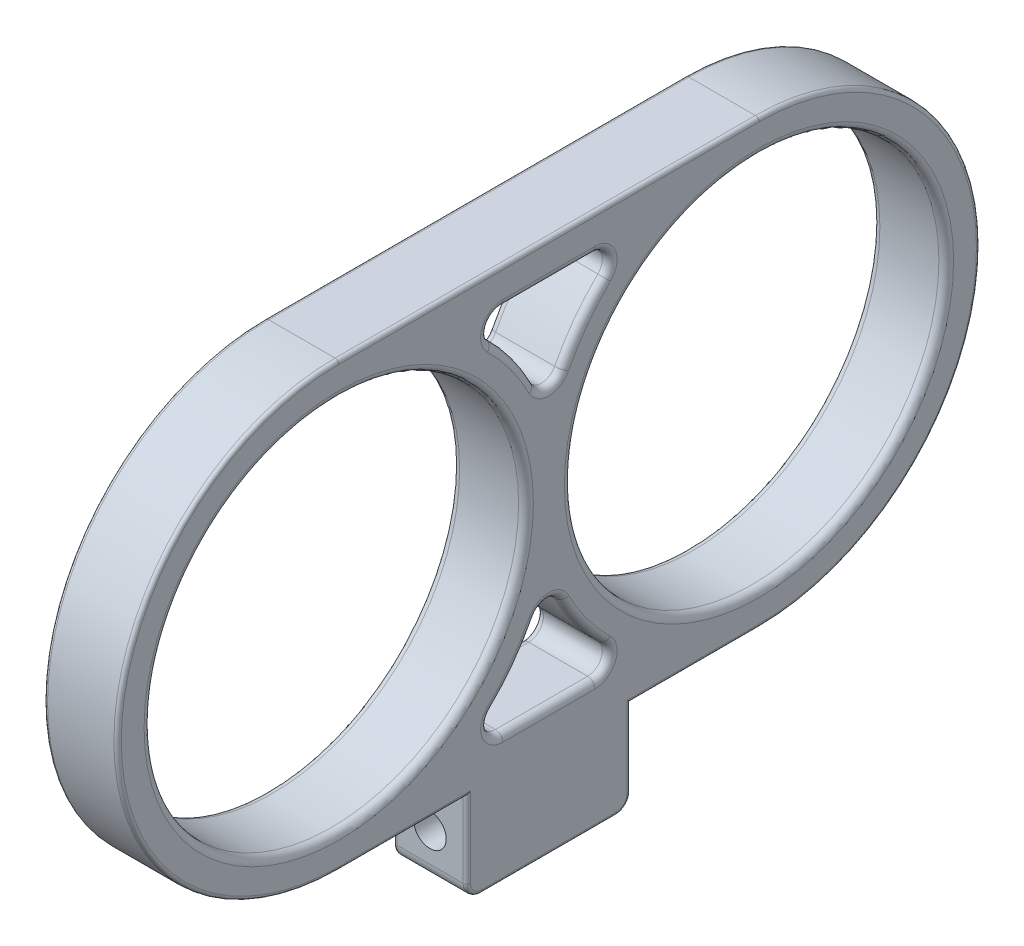
SolidWorks part; units mm, degrees
ref_plane "Front Plane" through (0, 0, 0) normal (0, 0, 1) x (1, 0, 0)
ref_plane "Top Plane" through (0, 0, 0) normal (0, 1, 0) x (1, 0, 0)
ref_plane "Right Plane" through (0, 0, 0) normal (1, 0, 0) x (0, 0, -1)
sketch "Sketch1" plane through (0, 0, 0) normal (1, 0, 0) x (0, 0, -1)
  line L0 (0, 0) -> (57, 0) construction
  line L1 (0, 30) -> (57, 30)
  line L2 (0, -30) -> (57, -30)
  line L3 (16.5831, 25) -> (40.4169, 25)
  line L4 (17.3748, -30) -> (39.6252, -30)
  line L5 (17.3748, -30) -> (17.3748, -42.3952)
  line L6 (17.3748, -42.3952) -> (39.6252, -42.3952)
  line L7 (39.6252, -30) -> (39.6252, -42.3952)
  line L8 (16.5831, -25) -> (40.4169, -25)
  circle A0 centre (0, 0) radius 25.4
  circle A1 centre (57, 0) radius 25.4
  arc A2 (0, 30) -> (0, -30) centre (0, 0) ccw
  arc A3 (57, -30) -> (57, 30) centre (57, 0) ccw
  arc A4 (28.5, 9.3675) -> (16.5831, 25) centre (0, 0) ccw
  arc A5 (28.5, 9.3675) -> (40.4169, 25) centre (57, 0) cw
  arc A6 (28.5, -9.3675) -> (16.5831, -25) centre (0, 0) cw
  arc A7 (28.5, -9.3675) -> (40.4169, -25) centre (57, 0) ccw
  point P5 (28.5, 0)
  point P15 (28.5, -42.3952)
  point P23 (0, 0)
  dimension "D1" = 50.8
  dimension "D3" = 30
  dimension "D7" = 30
  dimension "D2" = 57
  dimension "D4" = 22.2504
  dimension "D5" = 12.3952
  dimension "D6" = 5
extrude "Boss-Extrude1" add sketch "Sketch1" along normal blind 10 contours L2 A3 L1 A2 A0 A1 | L7 L2 L5 L6 region at (0, 0, -28.5) region at (0, -36.1976, -28.5)
fillet "Fillet1" radius 2 2 edges at (5, -42.3952, -39.6252) (5, -42.3952, -17.3748)
fillet "Fillet4" radius 2 6 edges at (5, -25, -40.4169) (5, -9.3675, -28.5) (5, -25, -16.5831) (5, 9.3675, -28.5) (5, 25, -40.4169) (5, 25, -16.5831)
fillet "Fillet3" radius 1 28 edges at (10, 0, -82.4) (0, 0, -82.4) (0, 0, -25.4) (10, 0, -25.4) (0, 12.5516, -28.5) (0, 17.8446, -24.1158) (0, 23.75, -20.3945) (0, 25, -28.5) (0, 23.75, -36.6055) (0, -23.75, -20.3945) (0, -17.8446, -24.1158) (0, -12.5516, -28.5) (0, -17.8446, -32.8842) (0, -23.75, -36.6055) (10, 17.8446, -32.8842) (10, 23.75, -36.6055) (10, 25, -28.5) (10, 23.75, -20.3945) (10, 17.8446, -24.1158) (10, -12.5516, -28.5) (10, -17.8446, -32.8842) (10, -23.75, -36.6055) (10, -25, -28.5) (10, -23.75, -20.3945) (0, 17.8446, -32.8842) (0, -25, -28.5) (10, 12.5516, -28.5) (10, -17.8446, -24.1158)
fillet "Fillet2" radius 0.5 20 edges at (0, -30, -48.3126) (0, 0, -87) (0, 30, -28.5) (0, 0, 30) (0, -35.1976, -39.6252) (0, -41.8094, -39.0394) (0, -42.3952, -28.5) (0, -41.8094, -17.9606) (10, -35.1976, -17.3748) (10, -41.8094, -17.9606) (10, -35.1976, -39.6252) (10, -41.8094, -39.0394) (10, -30, -48.3126) (10, 0, -87) (10, 30, -28.5) (10, 0, 30) (0, -30, -8.6874) (0, -35.1976, -17.3748) (10, -42.3952, -28.5) (10, -30, -8.6874)
sketch "Sketch2" plane through (0, 0, -17.3748) normal (0, 0, 1) x (1, 0, 0)
  line L0 (9.5, -30) -> (0.5, -30) construction
  circle A0 centre (5, -36.35) radius 2.2
  point P4 (5, -30)
  dimension "D2" = 4.4
  dimension "D1" = 6.35
extrude "Cut-Extrude1" cut sketch "Sketch2" against normal up to next
